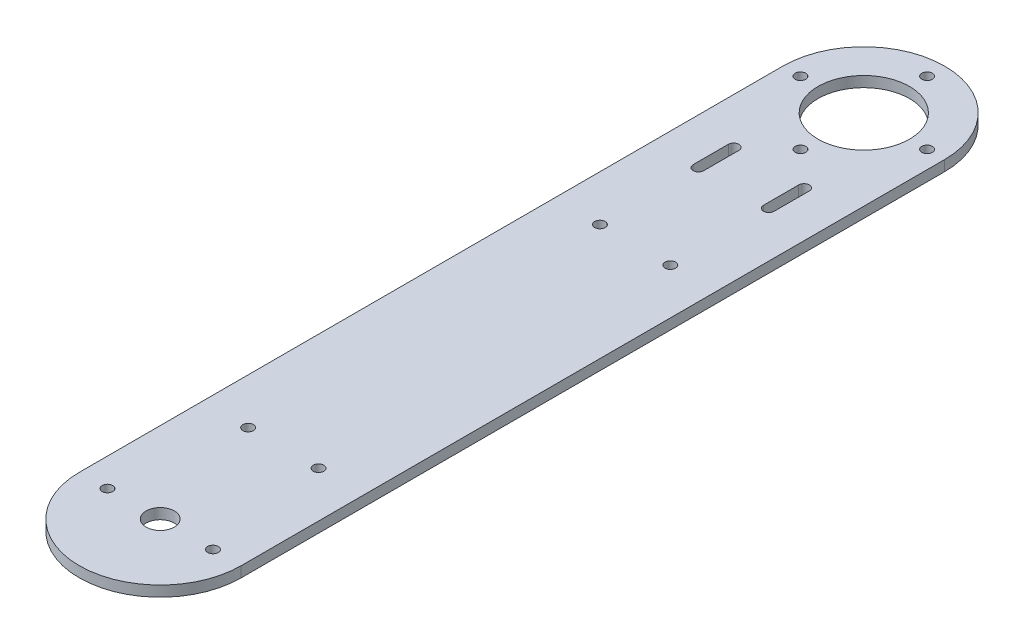
SolidWorks part; units mm, degrees
note: The reader was unsure of these and kept them because the rebuilt part matched: thickness of "基体-法兰1", "钣金6".
material "Hexcel AS4C (3000 丝)"
ref_plane "前视基准面" through (0, 0, 0) normal (0, 0, 1) x (1, 0, 0)
ref_plane "上视基准面" through (0, 0, 0) normal (0, 1, 0) x (1, 0, 0)
ref_plane "右视基准面" through (0, 0, 0) normal (1, 0, 0) x (0, 0, -1)
sketch "草图1" plane through (0, 0, 0) normal (0, 1, 0) x (1, 0, 0)
  line L0 (0, 0) -> (0, 200) construction
  line L1 (23, 200) -> (23, 0)
  line L2 (-23, 0) -> (-23, 200)
  line L3 (-10, 173) -> (-10, 163) construction
  line L4 (-8.5, 173) -> (-8.5, 163)
  line L5 (-11.5, 173) -> (-11.5, 163)
  line L6 (10, 163) -> (10, 173) construction
  line L7 (8.5, 163) -> (8.5, 173)
  line L8 (11.5, 163) -> (11.5, 173)
  arc A0 (-23, 0) -> (23, 0) centre (0, 0) ccw
  arc A1 (23, 200) -> (-23, 200) centre (0, 200) ccw
  circle A2 centre (0, 0) radius 4
  circle A4 centre (-10, 35) radius 1.5
  circle A5 centre (10, 35) radius 1.5
  circle A6 centre (-10, 135) radius 1.5
  circle A7 centre (10, 135) radius 1.5
  circle A8 centre (0, 200) radius 13
  arc A22 (-8.5, 173) -> (-11.5, 173) centre (-10, 173) ccw
  arc A23 (-11.5, 163) -> (-8.5, 163) centre (-10, 163) ccw
  circle A24 centre (15, 0) radius 1.5
  circle A25 centre (-15, 0) radius 1.5
  arc A26 (8.5, 163) -> (11.5, 163) centre (10, 163) ccw
  arc A27 (11.5, 173) -> (8.5, 173) centre (10, 173) ccw
  circle A28 centre (0, 218) radius 1.5
  circle A32 centre (18, 200) radius 1.5
  circle A33 centre (0, 182) radius 1.5
  circle A34 centre (-18, 200) radius 1.5
  point P19 (0, 15)
  point P22 (10, 168)
  point P28 (0, 200)
  point P29 (0, 174.0909)
  point P30 (0, 174.0909)
  point P31 (-10, 168)
  point P37 (0, 0)
  point P41 (0, 0)
  point P42 (-10, 168)
  point P53 (0, 192.5)
  point P54 (0, 200)
  dimension "D1" = 46
  dimension "D2" = 46
  dimension "D6" = 8
  dimension "D7" = 3
  dimension "D8" = 3
  dimension "D13" = 3
  dimension "D14" = 3
  dimension "D18" = 100
  dimension "D19" = 26
  dimension "D20" = 13
  dimension "D22" = 20
  dimension "D24" = 15
  dimension "D27" = 3
  dimension "D25" = 3
  dimension "D28" = 1.5
  dimension "D30" = 3
  dimension "D31" = 15
  dimension "D32" = 15
  dimension "D33" = 15
  dimension "D23" = 1.5
  dimension "D35" = 18
  dimension "D3" = 200
  dimension "D4" = 200
  dimension "D5" = 200
  dimension "D9" = 10
  dimension "D10" = 10
  dimension "D11" = 35
  dimension "D12" = 35
  dimension "D15" = 10
  dimension "D16" = 10
  dimension "D17" = 100
  dimension "D21" = 10
  dimension "D26" = 32
  dimension "D29" = 10
  dimension "D34" = 4
  dimension "D36" = 18
  dimension "D37" = 18
base flange "基体-法兰1" sketch "草图1" thickness 3 reverse thickness direction no parameters "D1"=0.7366
sketch "折弯-线1" [suppressed] plane through (0, 0, 0) normal (0, 1, 0) x (1, 0, 0)
sketch "边界框1" [suppressed] plane through (0, 0, 0) normal (0, 1, 0) x (1, 0, 0)
sheet metal parameters "钣金6" thickness 3 parameters "D1"=0.7366
flat pattern "平板型式6" [suppressed]
sketch "折弯-线2" plane through (0, 0, 0) normal (0, 1, 0) x (1, 0, 0)
sketch3d "边界框2" [suppressed]
  line L0 (-22, 22, 0) -> (-22, -222, 0) construction
  line L1 (22, 22, 0) -> (22, -222, 0) construction
  line L2 (-22, 22, 0) -> (22, 22, 0) construction
  line L3 (-22, -222, 0) -> (22, -222, 0) construction
